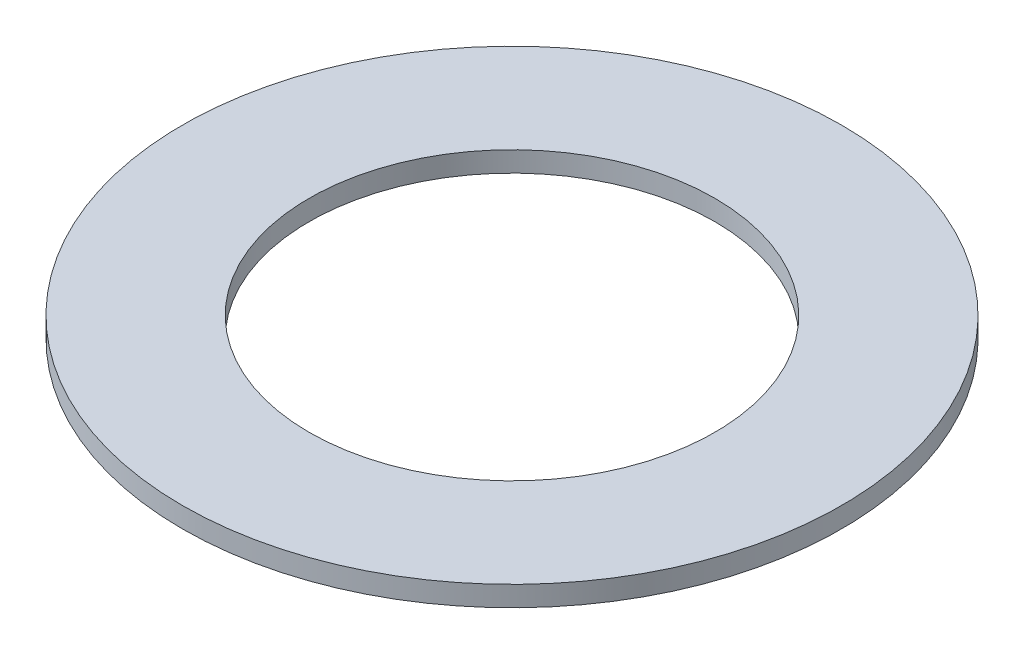
SolidWorks part; units mm, degrees
ref_plane "Front Plane" through (0, 0, 0) normal (0, 0, 1) x (1, 0, 0)
ref_plane "Top Plane" through (0, 0, 0) normal (0, 1, 0) x (1, 0, 0)
ref_plane "Right Plane" through (0, 0, 0) normal (1, 0, 0) x (0, 0, -1)
sketch "Sketch1" plane through (0, 0, 0) normal (0, 1, 0) x (1, 0, 0)
  circle A0 centre (0, 0) radius 65
  dimension "FLANGE_OD" = 130
extrude "Boss-Extrude1" add sketch "Sketch1" along normal blind 4
sketch "Sketch2" plane through (0, 0, 0) normal (0, 1, 0) x (1, 0, 0)
  circle A0 centre (0, 0) radius 40
  dimension "BORE_D" = 80
extrude "Cut-Extrude1" cut sketch "Sketch2" along normal through all
sketch "Sketch3" plane through (0, 4, 0) normal (0, 1, 0) x (1, 0, 0)
  circle A0 centre (0, 0) radius 23.0833 construction
  circle A1 centre (-23.0833, 0) radius 4.4644
  dimension "BOLT_D" = 8.9289
  dimension "BOLT_PCD" = 46.1666
extrude "Cut-Extrude2" cut sketch "Sketch3" against normal blind 3.3963 rebuild error yes
pattern_circular "CirPattern1" count 8 over 360 rebuild error yes
